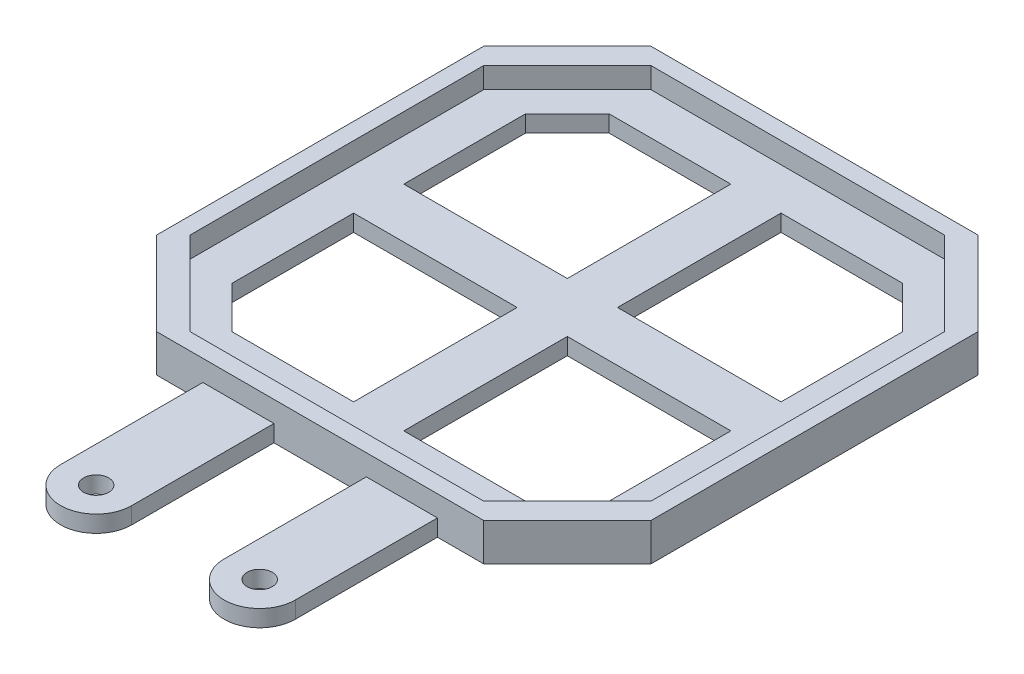
SolidWorks part; units mm, degrees
ref_plane "Alzado" through (0, 0, 0) normal (0, 0, 1) x (1, 0, 0)
ref_plane "Planta" through (0, 0, 0) normal (0, 1, 0) x (1, 0, 0)
ref_plane "Vista lateral" through (0, 0, 0) normal (1, 0, 0) x (0, 0, -1)
sketch "Croquis1" plane through (0, 0, 0) normal (0, 1, 0) x (1, 0, 0)
  line L0 (-0.5, 44.6) -> (9.5, 54.6)
  line L1 (0, 0) -> (54.1, 0)
  line L2 (0, 0) -> (0, 54.1)
  line L3 (0, 54.1) -> (54.1, 54.1)
  line L4 (54.1, 0) -> (54.1, 54.1)
  line L5 (54.6, 44.6) -> (44.6, 54.6)
  line L6 (44.6, -0.5) -> (54.6, 9.5)
  line L7 (9.5, -0.5) -> (-0.5, 9.5)
  line L8 (-0.5, 44.6) -> (0, 44.6)
  line L9 (9.5, -0.5) -> (44.6, -0.5)
  line L10 (-0.5, 9.5) -> (-0.5, 44.6)
  line L11 (9.5, 54.6) -> (44.6, 54.6)
  line L12 (54.6, 9.5) -> (54.6, 44.6)
  line L13 (4.5, 44.6) -> (4.5, 30.55)
  line L14 (4.5, 9.5) -> (9.5, 4.5)
  line L15 (9.5, 4.5) -> (23.55, 4.5)
  line L16 (44.6, 4.5) -> (49.6, 9.5)
  line L17 (49.6, 9.5) -> (49.6, 23.55)
  line L18 (4.5, 44.6) -> (9.5, 49.6)
  line L19 (9.5, 49.6) -> (23.55, 49.6)
  line L20 (44.6, 49.6) -> (49.6, 44.6)
  line L21 (4.5, 23.55) -> (4.5, 9.5)
  line L22 (4.5, 23.55) -> (23.55, 23.55)
  line L24 (4.5, 30.55) -> (23.55, 30.55)
  line L26 (30.55, 30.55) -> (49.6, 30.55)
  line L27 (30.55, 23.55) -> (49.6, 23.55)
  line L29 (30.55, 4.5) -> (30.55, 23.55)
  line L31 (23.55, 4.5) -> (23.55, 23.55)
  line L32 (30.55, 49.6) -> (44.6, 49.6)
  line L34 (23.55, 30.55) -> (23.55, 49.6)
  line L36 (30.55, 4.5) -> (44.6, 4.5)
  line L38 (30.55, 30.55) -> (30.55, 49.6)
  line L39 (49.6, 30.55) -> (49.6, 44.6)
  point P4 (54.6, 54.6)
  point P7 (-0.5, -0.5)
  point P10 (-0.5, 54.6)
  point P11 (54.6, -0.5)
  point P26 (27.05, 27.05)
  point P31 (27.05, 27.05)
extrude "Saliente-Extruir1" add sketch "Croquis1" along normal blind 2 contours L7 L1 L6 L4 L5 L3 L0 L2 | L10 L0 L11 L5 L12 L6 L9 L7 region at (27.05, 0, -27.05)
sketch "Croquis2" plane through (0, 2, 0) normal (0, 1, 0) x (1, 0, 0)
  line L0 (-2.5, 46.6) -> (7.5, 56.6)
  line L1 (9.5, 54.6) -> (54.6, 54.6)
  line L2 (-0.5, 44.6) -> (-0.5, -0.5)
  line L3 (-0.5, -0.5) -> (54.6, -0.5)
  line L4 (54.6, 54.6) -> (54.6, -0.5)
  line L13 (7.5, -2.5) -> (46.6, -2.5)
  line L14 (-2.5, 7.5) -> (-2.5, 46.6)
  line L15 (7.5, 56.6) -> (46.6, 56.6)
  line L16 (56.6, 7.5) -> (56.6, 46.6)
  line L17 (7.5, -2.5) -> (-2.5, 7.5)
  line L18 (-0.5, 44.6) -> (9.5, 54.6)
  line L19 (56.6, 46.6) -> (46.6, 56.6)
  line L20 (46.6, -2.5) -> (56.6, 7.5)
  point P0 (-0.5, 54.6)
  point P4 (56.6, 56.6)
  point P9 (-2.5, -2.5)
  point P13 (-2.5, 56.6)
  point P14 (56.6, -2.5)
  line M17 (-0.5, 9.5) -> (9.5, -0.5)
  line M18 (9.5, -0.5) -> (44.6, -0.5)
  line M19 (44.6, -0.5) -> (54.6, 9.5)
  line M20 (54.6, 9.5) -> (54.6, 44.6)
  line M21 (54.6, 44.6) -> (44.6, 54.6)
  line M22 (44.6, 54.6) -> (9.5, 54.6)
  line M23 (9.5, 54.6) -> (-0.5, 44.6)
  line M24 (-0.5, 44.6) -> (-0.5, 9.5)
extrude "Saliente-Extruir3" add sketch "Croquis2" along normal blind 2.5 and the other way blind 2 contours M24 M17 M18 M19 M20 M21 M22 M23 | L15 L19 L16 L20 L13 L17 L14 L0 region at (27.05, 2, -27.05)
sketch "Croquis4" plane through (0, 0, 0) normal (0, -1, 0) x (1, 0, 0)
  line L0 (27.05, 2.5) -> (7.5, 2.5)
  line L1 (7.5, 2.5) -> (46.6, 2.5) construction
  line L2 (46.6, 2.5) -> (27.05, 2.5)
  line L3 (17.275, 2.5) -> (17.275, 19.5) construction
  line L4 (32.575, 2.5) -> (32.575, 19.5)
  line L5 (13.025, 2.5) -> (13.025, 19.5)
  line L6 (21.525, 2.5) -> (21.525, 19.5)
  line L7 (36.825, 2.5) -> (36.825, 19.5) construction
  line L8 (41.075, 2.5) -> (41.075, 19.5)
  line L9 (13.025, 2.5) -> (21.525, 2.5)
  line L10 (32.575, 2.5) -> (41.075, 2.5)
  arc A1 (21.525, 19.5) -> (13.025, 19.5) centre (17.275, 19.5) ccw
  arc A3 (41.075, 19.5) -> (32.575, 19.5) centre (36.825, 19.5) ccw
  circle A4 centre (36.825, 19.5) radius 1.5
  circle A5 centre (17.275, 19.5) radius 1.5
  point P10 (36.825, 2.5)
  point P11 (17.275, 2.5)
extrude "Saliente-Extruir4" add sketch "Croquis4" against normal blind 2 contours L6 A1 L5 L0 A5 | L8 A3 L4 L2 A4 region at (17.275, 0, 12.4008) region at (36.825, 0, 12.4008)
sketch "Croquis6" plane through (0, 2, 0) normal (0, 1, 0) x (1, 0, 0)
  line L0 (-0.5, 44.6) -> (4.5, 44.6)
  line L1 (4.5, 44.6) -> (4.5, 30.05)
  line L2 (4.5, 9.5) -> (9.5, 4.5)
  line L3 (9.5, 4.5) -> (24.05, 4.5)
  line L4 (44.6, 4.5) -> (49.6, 9.5)
  line L5 (49.6, 9.5) -> (49.6, 24.05)
  line L6 (49.6, 44.6) -> (44.6, 49.6)
  line L7 (44.6, 49.6) -> (30.05, 49.6)
  line L8 (9.5, 49.6) -> (4.5, 44.6)
  line L9 (4.5, 24.05) -> (4.5, 9.5)
  line L10 (4.5, 24.05) -> (24.05, 24.05)
  line L12 (4.5, 30.05) -> (24.05, 30.05)
  line L14 (30.05, 30.05) -> (49.6, 30.05)
  line L15 (24.05, 49.6) -> (9.5, 49.6)
  line L17 (24.05, 4.5) -> (24.05, 24.05)
  line L19 (30.05, 4.5) -> (30.05, 24.05)
  line L21 (49.6, 30.05) -> (49.6, 44.6)
  line L22 (24.05, 30.05) -> (24.05, 49.6)
  line L24 (30.05, 24.05) -> (49.6, 24.05)
  line L25 (30.05, 30.05) -> (30.05, 49.6)
  line L26 (30.05, 4.5) -> (44.6, 4.5)
  point P3 (27.05, 27.05)
  point P15 (27.05, 27.05)
extrude "Cortar-Extruir1" cut sketch "Croquis6" against normal blind 2 contours L12 L22 L15 L8 L1 | L25 L14 L21 L6 L7 | L19 L26 L4 L5 L24 | L3 L17 L10 L9 L2 region at (14.5492, 2, -39.5508) region at (14.5492, 2, -14.5492) region at (39.5508, 2, -14.5492) region at (39.5508, 2, -39.5508)
